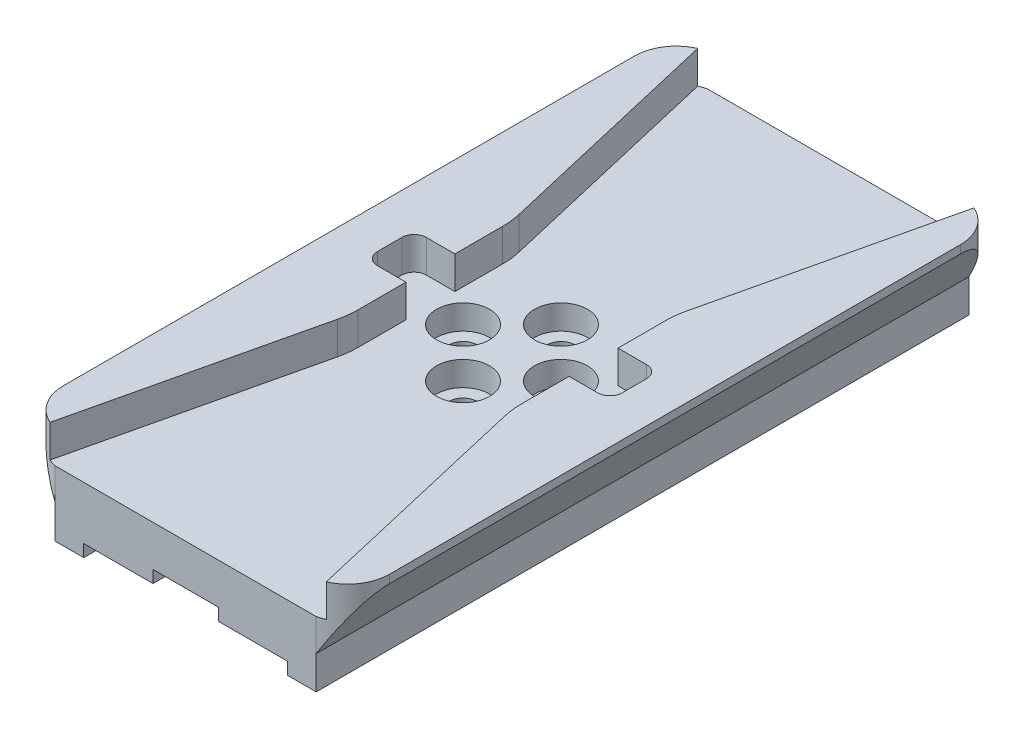
SolidWorks part; units mm, degrees
material "Сплав 2024"
ref_plane "Спереди" through (0, 0, 0) normal (0, 0, 1) x (1, 0, 0)
ref_plane "Сверху" through (0, 0, 0) normal (0, 1, 0) x (1, 0, 0)
ref_plane "Справа" through (0, 0, 0) normal (1, 0, 0) x (0, 0, -1)
sketch "Эскиз1" plane through (0, 0, 0) normal (0, 0, 1) x (1, 0, 0)
  line L0 (-20, 5) -> (-16, -1.9282)
  line L1 (-20, 6) -> (20, 6)
  line L2 (-25.6942, 6) -> (28.5829, 6) construction
  line L3 (-16, -6) -> (16, -6)
  line L4 (0, 6) -> (0, -6) construction
  line L5 (-22.304, 8.9907) -> (-15.6808, -2.4811) construction
  line L7 (-16, -1.9282) -> (-16, -6)
  line L9 (-20, 6) -> (-20, 5)
  line L10 (16, -1.9282) -> (16, -6)
  line L11 (20, 5) -> (16, -1.9282)
  line L12 (20, 6) -> (20, 5)
  point P15 (-20.5774, 6)
  dimension "D1" = 16
  dimension "D2" = 12
  dimension "D3" = 60
  dimension "D4" = 20.5774
  dimension "D6" = 20
  dimension "D7" = 1
extrude "Бобышка-Вытянуть1" add sketch "Эскиз1" along normal blind 80
sketch "Эскиз2" plane through (0, 6, 0) normal (0, 1, 0) x (1, 0, 0)
  line L0 (0, 0) -> (0, -80) construction
  line L1 (20, 0) -> (-20, 0) construction
  line L2 (20, -80) -> (-20, -80) construction
  line L3 (-17, 0) -> (-17, -80) construction
  line L4 (10, -50) -> (17, -80)
  line L5 (-17, 0) -> (-10, -30)
  line L6 (-10, -30) -> (-10, -50)
  line L7 (-10, -50) -> (-17, -80)
  line L8 (10, -30) -> (10, -50)
  line L9 (17, 0) -> (10, -30)
  line L10 (20, -40) -> (-20, -40) construction
  line L11 (-17, 0) -> (17, 0)
  line L12 (17, -80) -> (-17, -80)
  line L20 (-20, -80) -> (-20, 0) construction
  line L21 (20, -80) -> (20, 0) construction
  point P24 (-10, -40)
  dimension "D1" = 10
  dimension "D2" = 3
  dimension "D3" = 20
extrude "Вырез-Вытянуть1" cut sketch "Эскиз2" against normal blind 4
sketch "Эскиз3" plane through (0, 6, 0) normal (0, 1, 0) x (1, 0, 0)
  line L0 (20, -40) -> (-20, -40) construction
  line L4 (-10, -37) -> (-15, -37)
  line L5 (-10, -37) -> (-10, -43)
  line L6 (-10, -43) -> (-15, -43)
  line L7 (-15, -37) -> (-15, -43)
  line L8 (0, 0) -> (0, -80) construction
  line L9 (17, 0) -> (-17, 0) construction
  line L10 (-17, -80) -> (17, -80) construction
  line L11 (10, -37) -> (10, -43)
  line L12 (10, -43) -> (15, -43)
  line L13 (15, -37) -> (15, -43)
  line L14 (10, -37) -> (15, -37)
  line L15 (-10, -30) -> (-10, -50) construction
  line L16 (20, -80) -> (20, 0) construction
  line L17 (-20, -80) -> (-20, 0) construction
  point P12 (-10, -40)
  dimension "D1" = 6
  dimension "D2" = 5
extrude "Вырез-Вытянуть2" cut sketch "Эскиз3" against normal blind 4
fillet "Скругление1" [suppressed] radius 1.5
fillet "Скругление2" radius 10 4 edges at (10, 4, 50) (10, 4, 30) (-10, 4, 30) (-10, 4, 50)
sketch "Эскиз4" plane through (0, 2, 0) normal (0, 1, 0) x (1, 0, 0)
  line L0 (0, 0) -> (0, -80) construction
  line L1 (-17, -80) -> (17, -80) construction
  line L2 (20, -40) -> (-20, -40) construction
  line L5 (20, -80) -> (20, 0) construction
  line L6 (-20, -80) -> (-20, 0) construction
  circle A0 centre (0, -40) radius 6 construction
  dimension "D1" = 12
hole_wizard "Цековка для винта с внутренним шестигранником M31" positions "Эскиз6" profile "Эскиз5" counterbore size "M3" standard "Ansi Metric" end condition through all
sketch "Эскиз6" plane through (0, 2, 0) normal (0, 1, 0) x (1, 0, 0)
  line L0 (0, 0) -> (0, -80) construction
  line L1 (20, -40) -> (-20, -40) construction
  circle A0 centre (0, -40) radius 6 construction
  point P0 (0, -34)
  point P2 (6, -40)
  point P4 (0, -46)
  point P6 (-6, -40)
sketch "Эскиз5" plane through (0, 2, 34) normal (1, 0, 0) x (0, 0, 1)
  line L0 (0, 0) -> (0, 8)
  line L1 (0, 8) -> (1.7, 8)
  line L3 (1.7, 8) -> (1.7, 3)
  line L4 (1.7, 3) -> (3.25, 3)
  line L5 (3.25, 3) -> (3.25, 0)
  line L7 (3.25, 0) -> (0, 0)
  line L11 (0, -6.35) -> (0, 107.95) construction
  dimension "Диаметр сквозного отверстия" = 3.4
  dimension "Глубина сквозного отверстия" = 8
  dimension "Диаметр цековки" = 6.5
  dimension "Глубина цековки" = 3
sketch "Эскиз7" plane through (0, -6, 0) normal (0, -1, 0) x (1, 0, 0)
  line L0 (0, 80) -> (0, 0) construction
  line L2 (-11.5, 77) -> (11.5, 77)
  line L3 (-11.5, 77) -> (-11.5, 51)
  line L5 (-16, 80) -> (16, 80) construction
  line L6 (11.5, 77) -> (11.5, 51)
  line L7 (-11.5, 77) -> (11.5, 51) construction
  line L8 (-11.5, 51) -> (11.5, 77) construction
  arc A0 (-11.5, 51) -> (11.5, 51) centre (0, 19) cw
  point P0 (0, 64)
  dimension "D2" = 26
  dimension "D5" = 45
  dimension "D1" = 3
  dimension "D3" = 23
  dimension "D4" = 26
extrude "Вырез-Вытянуть3" cut sketch "Эскиз7" against normal blind 7
sketch "Эскиз8" plane through (0, 1, 0) normal (0, -1, 0) x (1, 0, 0)
  line L0 (0, 80) -> (0, 0) construction
  line L1 (-16, 80) -> (16, 80) construction
  line L2 (-16, 61.2) -> (16, 61.2) construction
  line L3 (-16, 80) -> (-16, 0) construction
  line L4 (16, 80) -> (16, 0) construction
  line L6 (13.1, 58.95) -> (7.1, 63.45) construction
  line L7 (-13.1, 63.45) -> (-7.1, 63.45)
  line L8 (-13.1, 63.45) -> (-13.1, 58.95)
  line L9 (-13.1, 58.95) -> (-7.1, 58.95)
  line L10 (13.1, 63.45) -> (7.1, 58.95) construction
  line L11 (-13.1, 63.45) -> (-7.1, 58.95) construction
  line L12 (-13.1, 58.95) -> (-7.1, 63.45) construction
  line L13 (13.1, 58.95) -> (7.1, 58.95)
  line L14 (13.1, 63.45) -> (13.1, 58.95)
  line L15 (13.1, 63.45) -> (7.1, 63.45)
  arc A0 (-7.1, 58.95) -> (-7.1, 63.45) centre (-7.1, 61.2) ccw
  arc A1 (7.1, 58.95) -> (7.1, 63.45) centre (7.1, 61.2) cw
  point P17 (-10.1, 61.2)
  point P24 (10.1, 61.2)
  dimension "D1" = 7.1
  dimension "D2" = 4.5
  dimension "D3" = 10.2
  dimension "D4" = 3
extrude "Бобышка-Вытянуть2" add sketch "Эскиз8" along normal blind 3
hole_wizard "Отверстие обработанное метчиком M3x0.53" positions "Эскиз10" profile "Эскиз9" tap size "M3x0.5" standard "Ansi Metric"
sketch "Эскиз10" plane through (0, -2, 0) normal (0, -1, 0) x (-1, 0, 0)
  point P0 (7.1, -61.2)
  point P2 (-7.1, -61.2)
sketch "Эскиз9" plane through (-7.1, -2, 61.2) normal (1, 0, 0) x (0, 0, -1)
  line L0 (0, 0) -> (0, 3.7511)
  line L1 (0, 3.7511) -> (1.25, 3)
  line L2 (1.25, 3) -> (1.25, 0)
  line L5 (1.25, 0) -> (0, 0)
  line L10 (0, 3.7511) -> (-1.25, 3) construction
  line L11 (0, -6.35) -> (0, 107.95) construction
  dimension "Диаметр сверла" = 2.5
  dimension "Глубина сверла" = 3
  dimension "Угол заточки сверла" = 118
cosmetic thread "Отверстие резьбы7" parameters "D1"=3, "D2"=3
cosmetic thread "Отверстие резьбы8" parameters "D1"=3, "D2"=3
sketch "Эскиз12" plane through (0, 1, 0) normal (0, -1, 0) x (1, 0, 0)
  line L0 (0, 77) -> (0, 51) construction
  line L1 (11.5, 77) -> (-11.5, 77) construction
  line L2 (-11.5, 51) -> (11.5, 51) construction
  line L3 (-1.8247, 64) -> (1.8247, 64) construction
  line L4 (-13.6614, 76) -> (7.1704, 76) construction
  line L5 (-11.5, 80.8402) -> (-11.5, 69.1924) construction
  line L6 (-11.5, 77) -> (-11.5, 51) construction
  circle A0 centre (-11.5, 76) radius 2
  circle A3 centre (11.5, 76) radius 2
  circle A4 centre (11.5, 52) radius 2
  circle A6 centre (-11.5, 52) radius 2
  point P14 (0, 64)
  dimension "D3" = 4
  dimension "D2" = 1
sketch "Эскиз15" plane through (0, 1, 0) normal (0, -1, 0) x (1, 0, 0)
  line L0 (0, 77) -> (0, 51) construction
  line L1 (11.5, 77) -> (-11.5, 77) construction
  line L2 (-13.8501, 64) -> (13.8501, 64) construction
  line L4 (-11.5, 51) -> (11.5, 51) construction
  line L5 (11.5, 51) -> (11.5, 77) construction
  line L7 (11.5, 77) -> (-11.5, 77) construction
  line L8 (-11.5, 77) -> (-11.5, 63.45) construction
  line L9 (-11.5, 77) -> (-11.5, 51) construction
  circle A0 centre (-11.5, 51) radius 2.5
  circle A1 centre (11.5, 51) radius 2.5
  circle A2 centre (-9, 77) radius 2.5
  circle A3 centre (9, 77) radius 2.5
  point P8 (0, 64)
  dimension "D1" = 5
  dimension "D2" = 5
  dimension "D3" = 5
extrude "Бобышка-Вытянуть5" add sketch "Эскиз15" along normal up to surface (7 mm away) up to face at (0, -6, 64.5009)
fillet "Скругление8" radius 3 12 edges at (11.5, -2.5, 53.5) (9.1178, -2.5, 51.7584) (-9.1178, -2.5, 51.7584) (-11.5, -2.5, 53.5) (-11.5, -0.5, 58.95) (11.5, -0.5, 58.95) (11.5, -0.5, 63.45) (-11.5, -0.5, 63.45) (-11.5, -2.5, 77) (11.5, -2.5, 77) (6.5, -2.5, 77) (-6.5, -2.5, 77)
sketch "Эскиз16" plane through (0, -6, 0) normal (0, -1, 0) x (1, 0, 0)
  line L0 (-16, 80) -> (16, 80) construction
  line L1 (-12.5, 80) -> (12.5, 80)
  line L70 (-12.5, 54.3541) -> (-12.5, 80)
  line L71 (12.5, 54.3541) -> (12.5, 80)
  line L72 (-11.5, 71.5228) -> (-11.5, 55.6098) construction
  line L73 (11.5, 55.6098) -> (11.5, 71.5228) construction
  arc A0 (7.2531, 52.2211) -> (-7.2531, 52.2211) centre (0, 19) ccw construction
  arc A1 (7.2531, 52.2211) -> (-7.2531, 52.2211) centre (0, 19) ccw construction
  arc A2 (8.0001, 51.0194) -> (-8.0001, 51.0194) centre (0, 19) ccw
  arc A3 (7.0398, 51.2441) -> (-7.0398, 51.2441) centre (0, 19) ccw construction
  arc A42 (-12.5, 54.3541) -> (-8.0001, 51.0194) centre (-11.5, 51) ccw
  arc A43 (8.0001, 51.0194) -> (12.5, 54.3541) centre (11.5, 51) ccw
  dimension "D3" = 7
  dimension "D4" = 7
  dimension "D6" = 1
  dimension "D7" = 1
  dimension "D2" = 1
extrude "Вырез-Вытянуть6" cut sketch "Эскиз16" against normal blind 1.5
fillet "Скругление9" radius 3 4 edges at (12.5, -5.25, 54.3541) (8.0001, -5.25, 51.0194) (-8.0001, -5.25, 51.0194) (-12.5, -5.25, 54.3541)
hole_wizard "Отверстие обработанное метчиком M3x0.52" positions "Эскиз19" profile "Эскиз18" tap size "M3x0.5" standard "Ansi Metric"
sketch "Эскиз19" plane through (0, -4.5, 0) normal (0, -1, 0) x (-1, 0, 0)
  point P0 (11.5, -51)
  point P3 (-11.5, -51)
  point P6 (-9, -77)
  point P9 (9, -77)
sketch "Эскиз18" plane through (-11.5, -4.5, 51) normal (1, 0, 0) x (0, 0, -1)
  line L0 (0, 0) -> (0, 6.2501)
  line L1 (0, 6.2501) -> (1.25, 5.499)
  line L2 (1.25, 5.499) -> (1.25, 0)
  line L5 (1.25, 0) -> (0, 0)
  line L10 (0, 6.2501) -> (-1.25, 5.499) construction
  line L11 (0, -6.35) -> (0, 107.95) construction
  dimension "Диаметр сверла" = 2.5
  dimension "Глубина сверла" = 5.499
  dimension "Угол заточки сверла" = 118
cosmetic thread "Отверстие резьбы9" parameters "D1"=5.5, "D2"=3
cosmetic thread "Отверстие резьбы10" parameters "D1"=5.5, "D2"=3
cosmetic thread "Отверстие резьбы11" parameters "D1"=5.5, "D2"=3
cosmetic thread "Отверстие резьбы12" parameters "D1"=5.5, "D2"=3
sketch "Эскиз20" plane through (0, -4.5, 0) normal (0, -1, 0) x (1, 0, 0)
  line L0 (0, 80) -> (0, 67.2176) construction
  line L1 (12.5, 80) -> (-12.5, 80) construction
  line L2 (-4.3902, 77) -> (4.3902, 77) construction
  line L3 (-4, 80) -> (4, 80)
  line L4 (-4, 80) -> (-4, 77)
  line L5 (-4, 77) -> (4, 77)
  line L6 (4, 80) -> (4, 77)
  line L7 (-4, 80) -> (4, 77) construction
  line L8 (-4, 77) -> (4, 80) construction
  point P5 (0, 78.5)
  dimension "D1" = 8
extrude "Вырез-Вытянуть7" cut sketch "Эскиз20" against normal blind 1.5
sketch "Эскиз21" plane through (0, -2, 0) normal (0, -1, 0) x (1, 0, 0)
  line L0 (11.5, 61.2) -> (-11.5, 61.2) construction
  line L1 (11.5, 55.95) -> (11.5, 66.45) construction
  line L2 (-11.5, 55.95) -> (-11.5, 66.45) construction
  line L3 (0, 53.0037) -> (0, 77) construction
  line L4 (4.3902, 77) -> (-4.3902, 77) construction
  line L6 (-5.5, 63.7) -> (5.5, 63.7)
  line L7 (-5.5, 63.7) -> (-5.5, 58.7)
  line L8 (-5.5, 58.7) -> (5.5, 58.7)
  line L9 (5.5, 63.7) -> (5.5, 58.7)
  line L10 (-5.5, 63.7) -> (5.5, 58.7) construction
  line L11 (-5.5, 58.7) -> (5.5, 63.7) construction
  arc A0 (7.2531, 52.2211) -> (-7.2531, 52.2211) centre (0, 19) ccw construction
  point P13 (0, 61.2)
  dimension "D1" = 11
  dimension "D2" = 5
extrude "Вырез-Вытянуть8" cut sketch "Эскиз21" against normal up to surface (3 mm away) up to face at (0, 1, 62.8736)
ref_plane "Плоскость1" through (0, 0, 40) normal (0, 0, 1) x (1, 0, 0)
mirror "Зеркальное отражение1" about plane through (0, 0, 40) normal (0, 0, 1) of "Вырез-Вытянуть3"
fillet "Скругление10" radius 3 4 edges at (11.5, -2.5, 3) (-11.5, -2.5, 3) (-11.5, -2.5, 29) (11.5, -2.5, 29)
sketch "Эскиз23" plane through (0, 6, 0) normal (0, 1, 0) x (1, 0, 0)
  line L0 (-17, 0) -> (-20, 0) construction
  line L1 (-20, -80) -> (-20, 0) construction
  line L2 (-16, 0) -> (-20, 0)
  line L3 (-20, 0) -> (-20, -5)
  line L4 (0, 0) -> (0, -80) construction
  line L5 (-17, -80) -> (17, -80) construction
  line L6 (20, -40) -> (-20, -40) construction
  line L7 (20, -80) -> (20, 0) construction
  line L8 (20, 0) -> (20, -5)
  line L9 (16, 0) -> (20, 0)
  line L10 (16, -80) -> (20, -80)
  line L11 (20, -80) -> (20, -75)
  line L12 (-20, -80) -> (-20, -75)
  line L13 (-16, -80) -> (-20, -80)
  arc A0 (-20, -5) -> (-16, 0) centre (-14.875, -5) cw
  arc A1 (20, -5) -> (16, 0) centre (14.875, -5) ccw
  arc A2 (20, -75) -> (16, -80) centre (14.875, -75) cw
  arc A3 (-20, -75) -> (-16, -80) centre (-14.875, -75) ccw
  dimension "D1" = 5
extrude "Вырез-Вытянуть10" cut sketch "Эскиз23" against normal through all
fillet "Скругление14" radius 1.5 4 edges at (-15, 4, 37) (-15, 4, 43) (15, 4, 37) (15, 4, 43)
